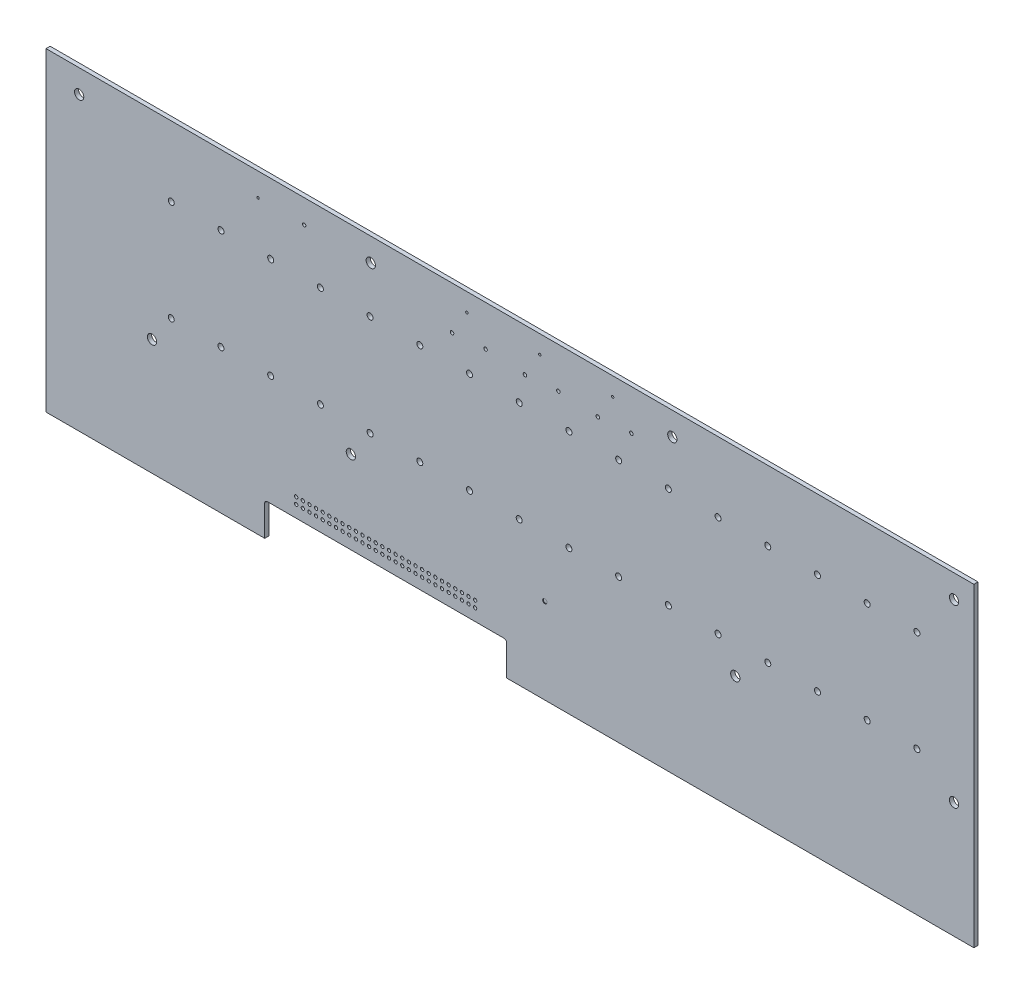
SolidWorks part; units mm, degrees
ref_plane "Front" through (0, 0, 0) normal (0, 0, 1) x (1, 0, 0)
ref_plane "Top" through (0, 0, 0) normal (0, 1, 0) x (1, 0, 0)
ref_plane "Right" through (0, 0, 0) normal (1, 0, 0) x (0, 0, -1)
sketch "Sketch1" plane through (0, 0, 0) normal (0, 0, 1) x (1, 0, 0)
  line L1 (0, 0) -> (355.6, 0)
  line L2 (0, 0) -> (0, -120.65)
  line L3 (0, -120.65) -> (355.6, -120.65)
  line L4 (355.6, 0) -> (355.6, -120.65)
  dimension "D1" = 120.65
  dimension "D2" = 355.6
extrude "Extrude1" add sketch "Sketch1" along normal blind 1.5748
sketch "DSPboard connector holes" plane through (0, 0, 1.5748) normal (0, 0, 1) x (1, 0, 0)
  line L0 (0, -120.65) -> (355.6, -120.65) construction
  line L1 (0, 0) -> (0, -120.65) construction
  circle A0 centre (48.006, -65.532) radius 1.15
  circle A1 centre (48.006, -26.802) radius 1.15
  dimension "D1" = 2.3
  dimension "D4" = 2.3
  dimension "D2" = 55.118
  dimension "D3" = 48.006
  dimension "D5" = 38.73
extrude "Cut-Extrude1" cut sketch "DSPboard connector holes" against normal blind 2.54
pattern_linear "LPattern1" count 16 spacing 19.05 along (1, 0, 0) of "Cut-Extrude1"
sketch "Sketch2" plane through (0, 0, 1.5748) normal (0, 0, 1) x (1, 0, 0)
  line L0 (0, -120.65) -> (355.6, -120.65) construction
  line L1 (0, 0) -> (0, -120.65) construction
  circle A0 centre (12.7, -8.89) radius 1.778
  circle A1 centre (124.46, -8.89) radius 1.778
  circle A2 centre (240.03, -8.89) radius 1.778
  circle A3 centre (347.98, -8.89) radius 1.778
  circle A4 centre (40.64, -76.2) radius 1.778
  circle A5 centre (116.84, -76.2) radius 1.778
  circle A6 centre (264.16, -76.2) radius 1.778
  circle A7 centre (347.98, -76.2) radius 1.778
  dimension "D1" = 3.556
  dimension "D4" = 3.556
  dimension "D5" = 3.556
  dimension "D6" = 3.556
  dimension "D10" = 3.556
  dimension "D11" = 3.556
  dimension "D12" = 3.556
  dimension "D13" = 3.556
  dimension "D2" = 111.76
  dimension "D3" = 12.7
  dimension "D7" = 124.46
  dimension "D8" = 240.03
  dimension "D9" = 347.98
  dimension "D14" = 44.45
  dimension "D15" = 40.64
  dimension "D16" = 116.84
  dimension "D17" = 264.16
  dimension "D18" = 347.98
extrude "PCB Mount holes" cut sketch "Sketch2" against normal blind 2.54
sketch "Sketch6" plane through (0, 0, 1.5748) normal (0, 0, 1) x (1, 0, 0)
  line L1 (0, 0) -> (0, -120.65) construction
  line L2 (355.6, 0) -> (0, 0) construction
  circle A4 centre (168.4383, -15.51) radius 0.675
  circle A5 centre (155.6083, -16.51) radius 0.675
  dimension "D2" = 16.51
  dimension "D8" = 1.35
  dimension "D9" = 1.35
  dimension "D11" = 12.83
  dimension "D14" = 155.6083
extrude "Peripheral-SATA" cut sketch "Sketch6" against normal blind 2.54
sketch "Sketch7" plane through (0, 0, 1.5748) normal (0, 0, 1) x (1, 0, 0)
  line L0 (355.6, 0) -> (0, 0) construction
  line L1 (0, 0) -> (0, -120.65) construction
  circle A0 centre (217.17, -6.985) radius 0.45
  circle A1 centre (189.23, -6.985) radius 0.45
  circle A2 centre (161.29, -6.985) radius 0.45
  circle A3 centre (81.28, -8.89) radius 0.45
  dimension "D1" = 0.9
  dimension "D4" = 0.8999
  dimension "D5" = 0.8999
  dimension "D6" = 0.8999
  dimension "D2" = 27.94
  dimension "D3" = 27.94
  dimension "D8" = 6.985
  dimension "D9" = 8.89
  dimension "D10" = 81.28
  dimension "D11" = 161.29
extrude "Off-board header holes" cut sketch "Sketch7" against normal blind 2.54
sketch "Sketch9" plane through (0, 0, 1.5748) normal (0, 0, 1) x (1, 0, 0)
  line L0 (0, -120.65) -> (355.6, -120.65) construction
  line L1 (84.836, -107.95) -> (175.514, -107.95)
  line L2 (83.82, -108.966) -> (83.82, -120.65)
  line L3 (83.82, -120.65) -> (176.53, -120.65)
  line L4 (176.53, -108.966) -> (176.53, -120.65)
  line L5 (0, 0) -> (0, -120.65) construction
  arc A0 (175.514, -107.95) -> (176.53, -108.966) centre (175.514, -108.966) cw
  arc A1 (83.82, -108.966) -> (84.836, -107.95) centre (84.836, -108.966) cw
  dimension "D1" = 1.016
  dimension "D2" = 1.016
  dimension "D3" = 92.71
  dimension "D4" = 83.82
  dimension "D5" = 12.7
extrude "NIC cutout" cut sketch "Sketch9" against normal blind 2.54
sketch "Sketch10" plane through (0, 0, 1.5748) normal (0, 0, 1) x (1, 0, 0)
  line L2 (175.514, -107.95) -> (84.836, -107.95) construction
  line L3 (176.53, -120.65) -> (176.53, -108.966) construction
  circle A0 centre (164.465, -100.838) radius 0.635
  dimension "D1" = 1.27
  dimension "D2" = 7.112
  dimension "D3" = 12.065
extrude "Header Holes" cut sketch "Sketch10" against normal blind 2.54
sketch "BGA mount pos" plane through (0, 0, 1.5748) normal (0, 0, 1) x (1, 0, 0)
  line L0 (0, 0) -> (0, -120.65) construction
  line L1 (176.53, -120.65) -> (355.6, -120.65) construction
  circle A0 centre (191.2, -87.85) radius 0.8381
  point P0 (191.2, -87.85)
  point P1 (0, -90.4568)
  dimension "D1" = 191.2
  dimension "D2" = 32.8
extrude "Cut-Extrude11" cut sketch "BGA mount pos" against normal blind 0.254
pattern_linear "LPattern3" count 28 spacing 2.54 along (-1, 0, 0) count 2 spacing 2.54 along (0, -1, 0) of "Header Holes"
pattern_linear "LPattern4" count 3 spacing 27.94 along (1, 0, 0) of "Peripheral-SATA"
sketch "Sketch11" plane through (0, 0, 0) normal (0, 0, -1) x (-1, 0, 0)
  line L0 (-355.6, 0) -> (0, 0) construction
  line L1 (0, 0) -> (0, -120.65) construction
  circle A0 centre (-98.94, -9.044) radius 0.635
  dimension "D3" = 1.27
  dimension "D1" = 9.044
  dimension "D2" = 98.94
extrude "JTAG hole" cut sketch "Sketch11" against normal blind 2.54
